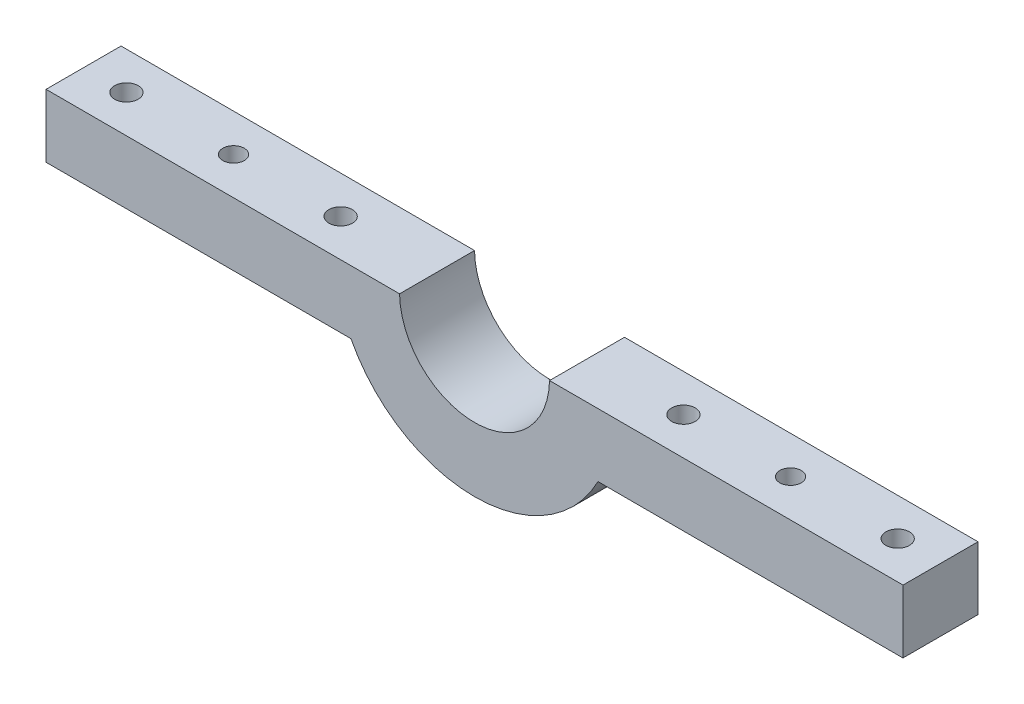
SolidWorks part; units mm, degrees
ref_plane "Plano frontal" through (0, 0, 0) normal (0, 0, 1) x (1, 0, 0)
ref_plane "Plano superior" through (0, 0, 0) normal (0, 1, 0) x (1, 0, 0)
ref_plane "Plano direito" through (0, 0, 0) normal (1, 0, 0) x (0, 0, -1)
sketch "Esboço1" plane through (0, 0, 0) normal (0, 0, 1) x (1, 0, 0)
  line L0 (-199.9977, -240.1091) -> (-34.9942, -240.2728)
  line L3 (200.0021, -240.5058) -> (199.9729, -270.0058)
  line L4 (199.9729, -270.0058) -> (57.6358, -269.8646)
  line L6 (-200.0269, -269.6091) -> (-199.9977, -240.1091)
  line L7 (34.9986, -240.3422) -> (200.0021, -240.5058)
  line L8 (-57.6898, -269.7503) -> (-200.0269, -269.6091)
  arc A1 (-34.9942, -240.2728) -> (34.9986, -240.3422) centre (0.0027, -239.8075) ccw
  arc A3 (-57.6898, -269.7503) -> (57.6358, -269.8646) centre (0.0027, -239.8075) ccw
  dimension "D5" = 35
  dimension "D6" = 65
  dimension "D1" = 200
  dimension "D2" = 400
  dimension "D3" = 0.5
  dimension "D4" = 29.5
  dimension "D7" = 29.5
  dimension "D8" = 0.5
extrude "Ressalto-extrusão1" add sketch "Esboço1" against normal blind 35
hole_wizard "Furo de diâmetro Ø11.0 (11)1" positions "Esboço2" profile "Esboço3" hole size "Ø11.0" standard "DIN" end condition through all
sketch "Esboço2" plane through (-0.2383, -240.3072, 0) normal (0.001, 1, 0) x (1, -0.001, 0)
  line L0 (-34.7559, 0) -> (-199.7595, 0) construction
  line L1 (-199.7595, 35) -> (-199.7595, 0) construction
  line L2 (200.2405, 35) -> (200.2405, 0) construction
  point P0 (-179.7595, 17.5)
  point P2 (-79.7595, 17.5)
  point P4 (80.2405, 17.5)
  point P6 (180.2405, 17.5)
  dimension "D1" = 17.5
  dimension "D2" = 20
  dimension "D3" = 100
  dimension "D4" = 20
  dimension "D5" = 100
sketch "Esboço3" plane through (-179.9977, -240.129, -17.5) normal (0, 0, 1) x (-1, 0.001, 0)
  line L0 (0, 0) -> (0, 64.6983)
  line L1 (0, 64.6983) -> (5.5, 64.6983)
  line L2 (5.5, 64.6983) -> (5.5, 0)
  line L5 (5.5, 0) -> (0, 0)
  line L11 (0, -6.35) -> (0, 107.95) construction
  dimension "Thru Hole Dia." = 11
  dimension "Thru Hole Depth" = 64.6983
hole_wizard "Furos-guia com Ø10.0mm1" positions "Esboço4" profile "Esboço5" hole size "Ø10.0" standard "DIN" end condition through all
sketch "Esboço4" plane through (-0.2676, -269.8072, 0) normal (-0.001, -1, 0) x (-1, 0.001, 0)
  line L0 (199.7595, 35) -> (57.4223, 35) construction
  line L1 (-200.2405, 35) -> (-200.2405, 0) construction
  line L2 (199.7595, 35) -> (199.7595, 0) construction
  point P0 (129.7595, 17.5)
  point P2 (-130.2405, 17.5)
  point P15 (-221.1813, -155.4184)
  dimension "D2" = 70
  dimension "D3" = 70
  dimension "D1" = 17.5
sketch "Esboço5" plane through (-130.027, -269.6785, -17.5) normal (0, 0, 1) x (1, -0.001, 0)
  line L0 (0, 0) -> (0, 29.8967)
  line L1 (0, 29.8967) -> (5, 29.8967)
  line L2 (5, 29.8967) -> (5, 0)
  line L5 (5, 0) -> (0, 0)
  line L11 (0, -6.35) -> (0, 107.95) construction
  dimension "Thru Hole Dia." = 10
  dimension "Thru Hole Depth" = 29.8967
hole_wizard "Furo de diâmetro Ø11.0 (11)2" positions "Esboço6" profile "Esboço7" hole size "Ø11.0" standard "DIN"
sketch "Esboço6" plane through (-0.2676, -269.8072, 0) normal (-0.001, -1, 0) x (-1, 0.001, 0)
  point P0 (129.7595, 17.5)
  point P3 (-130.2405, 17.5)
sketch "Esboço7" plane through (-130.027, -269.6785, -17.5) normal (0, 0, 1) x (1, -0.001, 0)
  line L0 (0, 0) -> (0, 13.3047)
  line L1 (0, 13.3047) -> (5.5, 10)
  line L2 (5.5, 10) -> (5.5, 0)
  line L5 (5.5, 0) -> (0, 0)
  line L10 (0, 13.3047) -> (-5.5, 10) construction
  line L11 (0, -6.35) -> (0, 107.95) construction
  dimension "Hole Dia." = 11
  dimension "Hole Depth" = 10
  dimension "Drill Angle" = 118
sketch "Esboço8" plane through (0, 0, -35) normal (0, 0, -1) x (-1, 0, 0)
  line L1 (0.0973, -271.4968) -> (-0.1027, -271.4968)
  line L2 (0.0973, -271.4968) -> (0.0973, -308.1033)
  line L3 (0.0973, -308.1033) -> (-0.1027, -308.1033)
  line L4 (-0.1027, -271.4968) -> (-0.1027, -308.1033)
  line L5 (-0.0027, -239.8075) -> (-0.0027, -364.9303) construction
  dimension "D1" = 0.1
  dimension "D2" = 0.2
extrude "Corte-extrusão1" cut sketch "Esboço8" against normal blind 0.2
ref_axis "Eixo1" through (0.0027, -239.8075, 652.5) along (0, 0, -1)
ref_axis "Eixo2" through (0.0027, -239.8075, 652.5) along (0, 0, -1)
